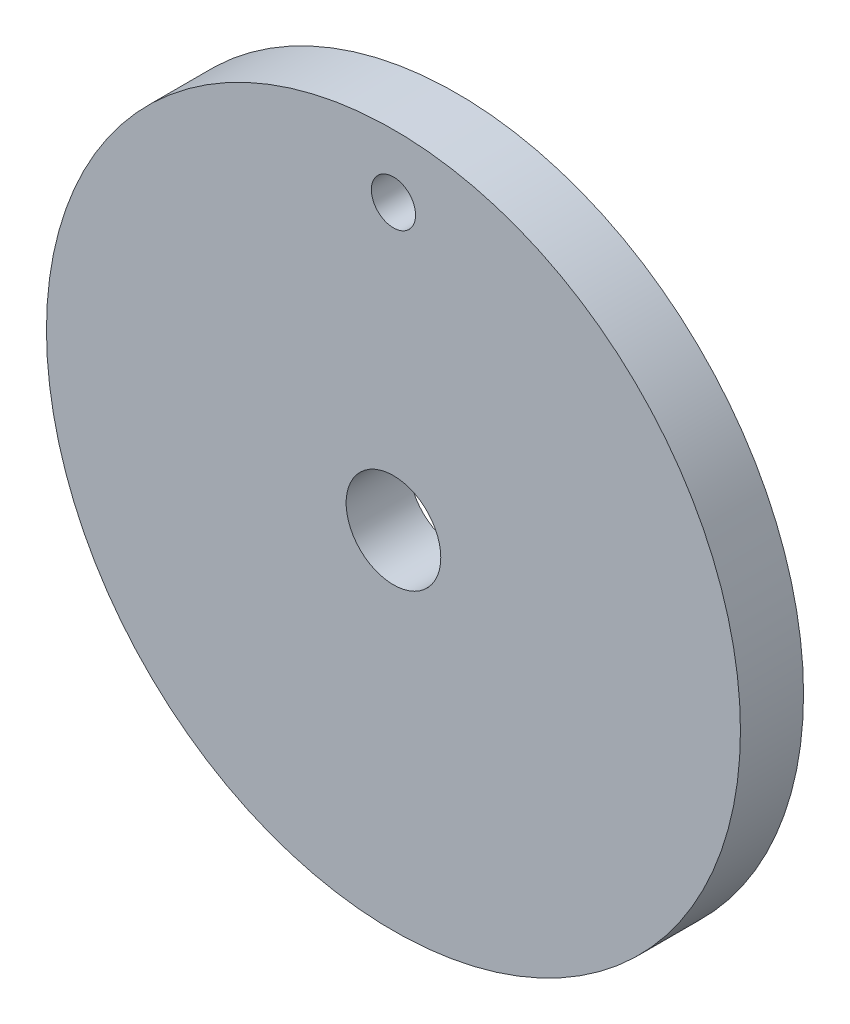
SolidWorks part; units mm, degrees
material "Acrylic (Medium-high impact)"
ref_plane "Front Plane" through (0, 0, 0) normal (0, 0, 1) x (1, 0, 0)
ref_plane "Top Plane" through (0, 0, 0) normal (0, 1, 0) x (1, 0, 0)
ref_plane "Right Plane" through (0, 0, 0) normal (1, 0, 0) x (0, 0, -1)
sketch "Sketch1" plane through (0, 0, 0) normal (0, 0, 1) x (1, 0, 0)
  circle A0 centre (0, 0) radius 11
  circle A1 centre (0, 0) radius 1.5
  circle A2 centre (0, 9) radius 0.7
  dimension "D1" = 3
  dimension "D2" = 22
  dimension "D3" = 1.4
  dimension "D4" = 9
extrude "Boss-Extrude1" add sketch "Sketch1" along normal blind 2
